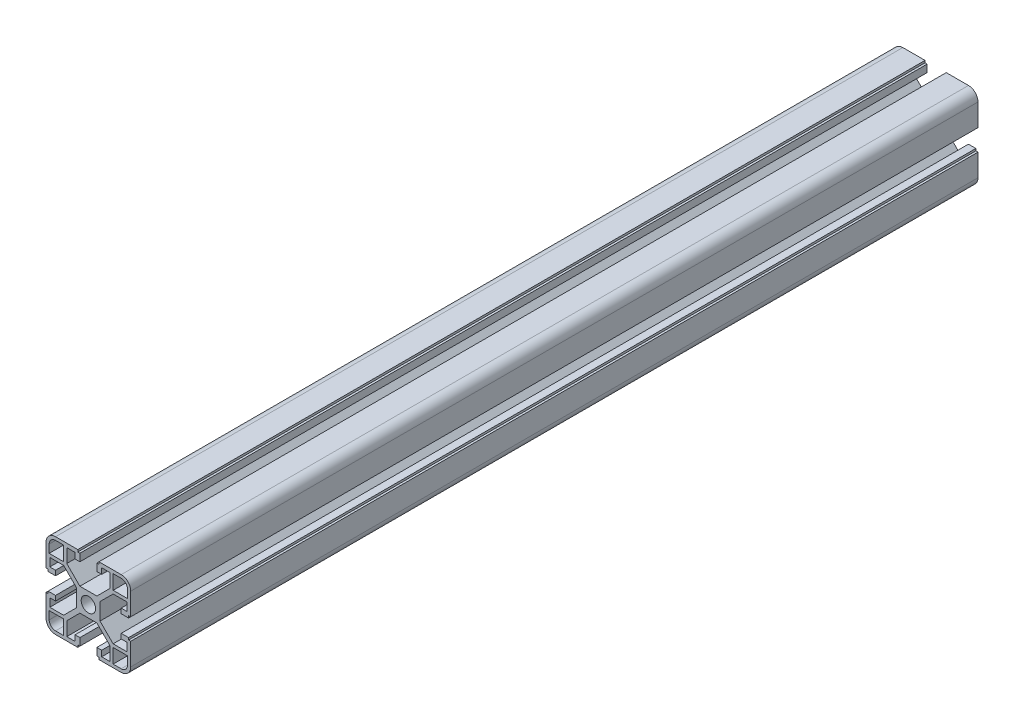
SolidWorks part; units mm, degrees
material "6061-T6 (SS)"
ref_plane "Front Plane" through (0, 0, 0) normal (0, 0, 1) x (1, 0, 0)
ref_plane "Top Plane" through (0, 0, 0) normal (0, 1, 0) x (1, 0, 0)
ref_plane "Right Plane" through (0, 0, 0) normal (1, 0, 0) x (0, 0, -1)
sketch "Sketch1" plane through (0, 0, 0) normal (0, 0, 1) x (1, 0, 0)
  line L0 (3.4, 0) -> (5.5, 0)
  line L1 (10.19, 11.69) -> (4, 5.5)
  line L2 (11.69, 10.19) -> (5.5, 4)
  line L3 (18.2, 10.19) -> (11.69, 10.19)
  line L4 (18.2, 10.19) -> (18.2, 6.3)
  line L5 (18.2, 6.3) -> (15.5, 6.3)
  line L6 (15.5, 6.3) -> (15.5, 4)
  line L7 (15.5, 4) -> (19, 4)
  line L8 (19, 4) -> (19, 5)
  line L9 (19, 5) -> (20, 5)
  line L10 (20, 5) -> (20, 15.5)
  line L11 (15.5, 20) -> (5, 20)
  line L12 (18.5, 11.69) -> (18.5, 15.5)
  line L13 (15.5, 18.5) -> (11.69, 18.5)
  line L14 (11.69, 11.69) -> (11.69, 18.5)
  line L15 (0, 3.4) -> (0, 5.5)
  line L16 (4, 5.5) -> (0, 5.5)
  line L17 (5, 20) -> (5, 19)
  line L18 (5.5, 0) -> (5.5, 4)
  line L19 (5, 19) -> (4, 19)
  line L20 (4, 19) -> (4, 15.5)
  line L21 (4, 15.5) -> (6.3, 15.5)
  line L22 (10.19, 11.69) -> (10.19, 18.2)
  line L23 (11.69, 11.69) -> (18.5, 11.69)
  line L24 (6.3, 18.2) -> (6.3, 15.5)
  line L25 (10.19, 18.2) -> (6.3, 18.2)
  arc A0 (20, 15.5) -> (15.5, 20) centre (15.5, 15.5) ccw
  arc A1 (18.5, 15.5) -> (15.5, 18.5) centre (15.5, 15.5) ccw
  arc A2 (3.4, 0) -> (0, 3.4) centre (0, 0) ccw
  point P4 (0, 4.45)
  dimension "D3" = 4.5
  dimension "D18" = 1.5
  dimension "D9" = 3.4
  dimension "D20" = 1.8
  dimension "D25" = 3
  dimension "D1" = 5.5
  dimension "D2" = 1.5
  dimension "D4" = 14.5
  dimension "D5" = 1.5
  dimension "D6" = 2.1
  dimension "D7" = 2.3
  dimension "D8" = 1.8
  dimension "D10" = 6.81
  dimension "D11" = 2.1
  dimension "D12" = 1
  dimension "D13" = 4.5
  dimension "D14" = 45
  dimension "D15" = 14.5
  dimension "D16" = 1
  dimension "D17" = 1.5
  dimension "D19" = 6.81
  dimension "D21" = 4.5
  dimension "D22" = 2.3
  dimension "D23" = 1
  dimension "D24" = 1
  dimension "D26" = 8.754
  dimension "D27" = 8.754
  dimension "D28" = 4
  dimension "D29" = 4
extrude "Boss-Extrude1" add sketch "Sketch1" along normal blind 400
mirror "Mirror1" about plane through (0, 0, 0) normal (0, 1, 0) of "Boss-Extrude1"
mirror "Mirror2" about plane through (0, 0, 0) normal (1, 0, 0) of "Boss-Extrude1"
mirror "Mirror3" about plane through (0, 0, 0) normal (0, 1, 0) of "Mirror2"
